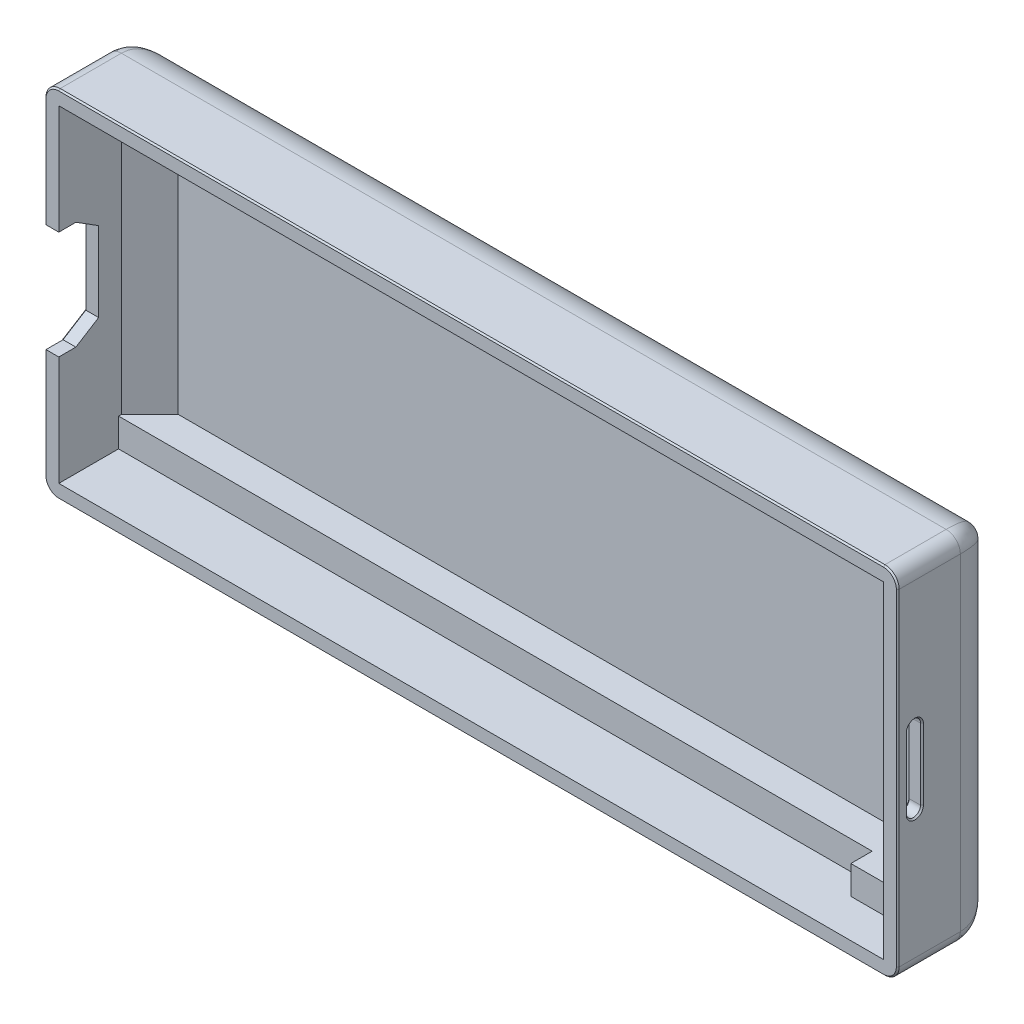
SolidWorks part; units mm, degrees
material "ABS"
ref_plane "Спереди" through (0, 0, 0) normal (0, 0, 1) x (1, 0, 0)
ref_plane "Сверху" through (0, 0, 0) normal (0, 1, 0) x (1, 0, 0)
ref_plane "Справа" through (0, 0, 0) normal (1, 0, 0) x (0, 0, -1)
sketch "Эскиз2" plane through (0, 0, 0) normal (0, 0, 1) x (1, 0, 0)
  line L1 (-30, 12.5) -> (30, 12.5)
  line L2 (-30, 12.5) -> (-30, -12.5)
  line L3 (-30, -12.5) -> (30, -12.5)
  line L4 (30, 12.5) -> (30, -12.5)
  line L5 (-30, 12.5) -> (30, -12.5) construction
  line L6 (-30, -12.5) -> (30, 12.5) construction
  point P0 (0, 0)
  dimension "D1" = 60
  dimension "D2" = 25
extrude "Бобышка-Вытянуть1" add sketch "Эскиз2" along normal blind 1
sketch "Эскиз3" plane through (0, 0, 1) normal (0, 0, 1) x (1, 0, 0)
  line L0 (-30, 12.5) -> (30, 12.5)
  line L1 (30, 12.5) -> (30, -12.5)
  line L2 (30, -12.5) -> (-30, -12.5)
  line L3 (-30, -12.5) -> (-30, 12.5)
  line L4 (-29, 11.5) -> (29, 11.5)
  line L5 (29, 11.5) -> (29, -11.5)
  line L6 (29, -11.5) -> (-29, -11.5)
  line L7 (-29, -11.5) -> (-29, 11.5)
  dimension "D1" = 1
  dimension "D2" = 1
  dimension "D3" = 1
  dimension "D4" = 1
  dimension "D5" = 58
extrude "Бобышка-Вытянуть2" add sketch "Эскиз3" along normal blind 6.4
sketch "Эскиз4" plane through (0, 0, 1) normal (0, 0, 1) x (1, 0, 0)
  line L0 (29, -11.5) -> (29, 11.5) construction
  line L1 (-29, 11.5) -> (29, 11.5)
  line L2 (-29, 11.5) -> (-29, 9.5)
  line L3 (-29, 9.5) -> (29, 9.5)
  line L4 (29, 11.5) -> (29, 9.5)
  line L6 (-29, -11.5) -> (29, -11.5)
  line L7 (-29, -11.5) -> (-29, -9.5)
  line L8 (-29, -9.5) -> (29, -9.5)
  line L9 (29, -11.5) -> (29, -9.5)
  point P11 (0, 11.5)
  dimension "D1" = 2
  dimension "D2" = 2
extrude "Бобышка-Вытянуть3" add sketch "Эскиз4" along normal blind 2.2
sketch "Эскиз6" plane through (0, 0, 3.2) normal (0, 0, 1) x (1, 0, 0)
  line L0 (-29, 9.5) -> (29, 9.5) construction
  line L1 (29, 11.5) -> (24, 11.5)
  line L2 (29, 11.5) -> (29, 9.5)
  line L3 (29, 9.5) -> (24, 9.5)
  line L4 (24, 11.5) -> (24, 9.5)
  line L5 (29, -9.5) -> (-29, -9.5) construction
  line L6 (29, -11.5) -> (24, -11.5)
  line L7 (29, -11.5) -> (29, -9.5)
  line L8 (29, -9.5) -> (24, -9.5)
  line L9 (24, -11.5) -> (24, -9.5)
  line L10 (-29, 11.5) -> (-29, -11.5) construction
  dimension "D1" = 53
  dimension "D2" = 53
extrude "Бобышка-Вытянуть4" add sketch "Эскиз6" along normal blind 1.5
fillet "Скругление1" radius 1 4 edges at (-30, 12.5, 3.7) (30, 12.5, 3.7) (-30, -12.5, 3.7) (30, -12.5, 3.7)
fillet "Скругление3" radius 3 8 edges at (-29.7071, -12.2071, 0) (-30, 0, 0) (-29.7071, 12.2071, 0) (0, 12.5, 0) (29.7071, 12.2071, 0) (30, 0, 0) (29.7071, -12.2071, 0) (0, -12.5, 0)
sketch "Эскиз8" plane through (-29, 0, 0) normal (1, 0, 0) x (0, 0, -1)
  line L1 (-6.2, 3.8) -> (-4.6, 2.8)
  line L7 (-7.4, 3.8) -> (-6.2, 3.8)
  line L9 (2.0356, 0) -> (-15.2117, 0) construction
  line L10 (-7.4, 3.8) -> (-7.4, -3.8)
  line L11 (-7.4, -3.8) -> (-6.2, -3.8)
  line L12 (-6.2, -3.8) -> (-4.6, -2.8)
  line L13 (-4.6, -2.8) -> (-4.6, 2.8)
  line L15 (-1, 9.5) -> (-1, -9.5) construction
  point P8 (-4.6, 0)
  point P13 (-7.4, 0)
  dimension "D1" = 3.6
  dimension "D2" = 1
  dimension "D3" = 3.8
  dimension "D4" = 2.8
  dimension "D5" = 1.2
chamfer "Фаска2" distance 2 angle 45 2 edges at (29, 0, 1) (-29, 0, 1)
extrude "Вырез-Вытянуть3" cut sketch "Эскиз8" against normal through all
chamfer "Фаска3" distance 0.1 angle 45 14 edges at (29.7071, -12.2071, 7.4) (0, -12.5, 7.4) (-29.7071, -12.2071, 7.4) (-30, -7.65, 7.4) (-30, -3.8, 6.8) (-30, -3.3, 5.4) (-30, 0, 4.6) (-30, 3.3, 5.4) (-30, 3.8, 6.8) (-30, 7.65, 7.4) (-29.7071, 12.2071, 7.4) (30, 0, 7.4) (29.7071, 12.2071, 7.4) (0, 12.5, 7.4)
sketch "Эскиз9" plane through (30, 0, 0) normal (1, 0, 0) x (0, 0, -1)
  line L2 (-6.2, 2.5) -> (-6.2, -2.5) construction
  line L3 (-5.7, 2.5) -> (-5.7, -2.5)
  line L4 (-6.7, 2.5) -> (-6.7, -2.5)
  arc A0 (-5.7, 2.5) -> (-6.7, 2.5) centre (-6.2, 2.5) ccw
  arc A1 (-6.7, -2.5) -> (-5.7, -2.5) centre (-6.2, -2.5) ccw
  point P6 (-6.2, 0)
  dimension "D2" = 0.5
  dimension "D1" = 5
  dimension "D3" = 5
  dimension "D4" = 6.2
extrude "Вырез-Вытянуть4" cut sketch "Эскиз9" against normal up to next
chamfer "Фаска4" distance 0.1 angle 45 8 edges at (29, 3, 6.2) (29, 0, 6.7) (29, -3, 6.2) (29, 0, 5.7) (30, 3, 6.2) (30, 0, 6.7) (30, -3, 6.2) (30, 0, 5.7)
equation "\"D2@Эскиз3\"=\"D1@Эскиз3\""
equation "\"D3@Эскиз3\"=\"D1@Эскиз3\""
equation "\"D4@Эскиз3\"=\"D1@Эскиз3\""
equation "\"D2@Эскиз4\"=\"D1@Эскиз4\""
equation "\"D2@Эскиз6\"=\"D1@Эскиз6\""
